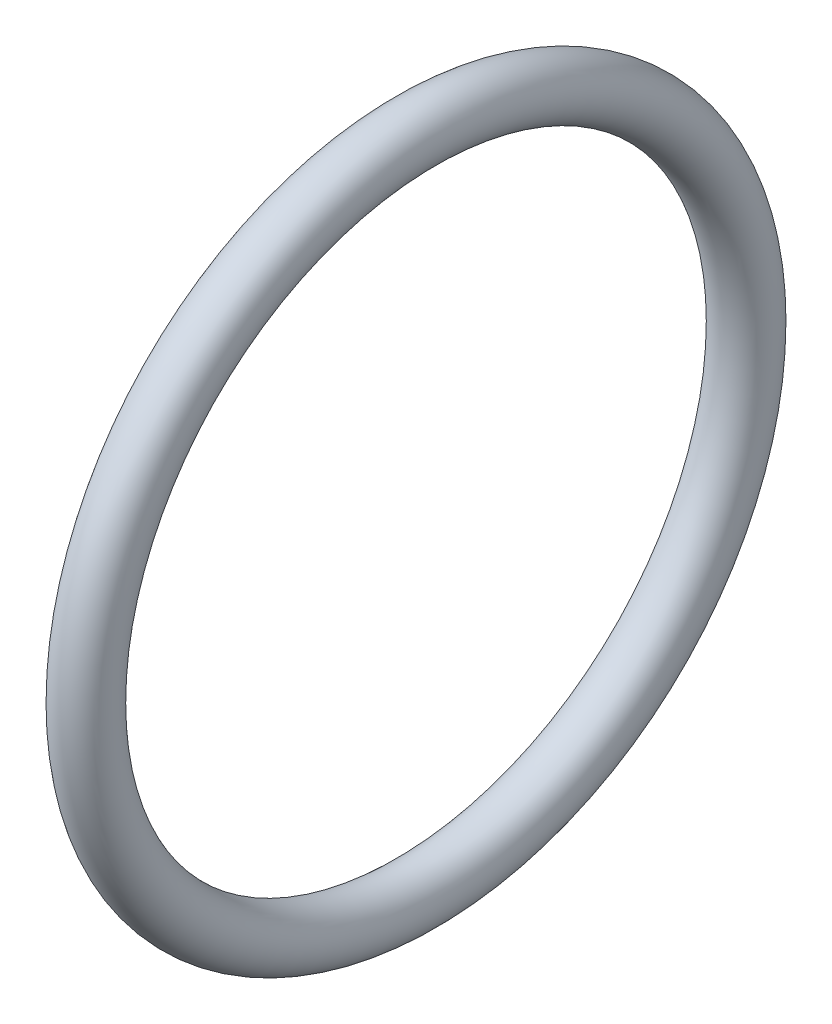
SolidWorks part; units mm, degrees
ref_plane "Front Plane" through (0, 0, 0) normal (0, 0, 1) x (1, 0, 0)
ref_plane "Top Plane" through (0, 0, 0) normal (0, 1, 0) x (1, 0, 0)
ref_plane "Right Plane" through (0, 0, 0) normal (1, 0, 0) x (0, 0, -1)
sketch "Sketch2" plane through (0, 0, 0) normal (0, 0, 1) x (1, 0, 0)
  line L0 (0, 0) -> (58.591, 0) construction
  line L2 (0, 0) -> (18.4, 0)
  line L3 (0, 0) -> (0, 2.5)
  line L4 (0, 2.5) -> (18.4, 2.5)
  line L5 (18.4, 0) -> (18.4, 2.5)
  line L6 (6.0094, 2.5) -> (6.0094, 6)
  line L11 (6.0094, 6) -> (9.9794, 6)
  line L16 (12.9794, 6) -> (12.9794, 3)
  line L17 (12.9794, 3) -> (13.6398, 3)
  line L18 (13.6398, 3) -> (13.6398, 2.5)
  line L19 (13.6398, 2.5) -> (6.0094, 2.5)
  line L22 (13.6398, 2.5) -> (16.1198, 2.5)
  line L23 (13.6398, 2.5) -> (13.6398, 4)
  line L24 (13.6398, 4) -> (16.1198, 4)
  line L25 (16.1198, 2.5) -> (16.1198, 4)
  line L27 (6.0094, 6) -> (9.9794, 6)
  line L28 (6.0094, 6) -> (6.0094, 9)
  line L29 (6.0094, 9) -> (9.9794, 9)
  line L30 (9.9794, 6) -> (9.9794, 9)
  line L31 (6.0094, 9) -> (6.0094, 8.25)
  line L32 (6.0094, 8.25) -> (5.0094, 8.25)
  line L33 (8.6609, 22.001) -> (8.6609, 12.476) construction
  line L34 (5.0094, 12.476) -> (12.3124, 12.476)
  line L35 (9.9794, 9) -> (12.3124, 9)
  line L36 (5.0094, 7.9375) -> (1.8344, 7.9375)
  line L37 (5.0094, 8.25) -> (5.0094, 12.476)
  line L38 (5.0094, 7.9375) -> (5.0094, 13.9365)
  line L39 (5.0094, 13.9365) -> (1.8344, 13.9365)
  line L40 (1.8344, 7.9375) -> (1.8344, 13.9365)
  line L41 (5.0094, 22.001) -> (12.3124, 22.001)
  line L42 (5.0094, 22.001) -> (5.0094, 30.1625)
  line L43 (5.0094, 30.1625) -> (12.3124, 30.1625)
  line L44 (12.3124, 22.001) -> (12.3124, 30.1625)
  line L49 (16.6398, 22.001) -> (16.6398, 7.5)
  line L51 (23.0198, 7.5) -> (23.0198, 6.5)
  line L54 (16.1198, 4) -> (13.6398, 4)
  line L56 (18.0398, 7.5) -> (23.0198, 7.5)
  line L57 (13.3124, 22.001) -> (16.6398, 22.001)
  line L58 (16.1198, 3.5) -> (20.0198, 3.5)
  line L59 (29.9098, 14) -> (26.9098, 11)
  line L60 (4.0094, 31.75) -> (18.0398, 31.75)
  line L61 (18.0398, 7.5) -> (23.0198, 7.5)
  line L62 (18.0398, 7.5) -> (18.0398, 12)
  line L63 (18.0398, 12) -> (23.0198, 12)
  line L64 (23.0198, 7.5) -> (23.0198, 12)
  line L65 (18.0398, 31.75) -> (18.0398, 12)
  line L66 (23.0198, 11) -> (26.9098, 11)
  line L67 (34.8098, 23) -> (31.3098, 19.5)
  line L68 (35.8098, 31) -> (38.7998, 33.99)
  line L69 (29.9098, 14) -> (29.9098, 15)
  line L70 (29.9098, 15) -> (22.9398, 15)
  line L71 (22.9398, 15) -> (21.0398, 15)
  line L72 (18.0398, 7.5) -> (16.6398, 7.5)
  line L73 (21.0398, 15) -> (21.0398, 43)
  line L74 (19.5798, 40) -> (9.6198, 40)
  line L75 (9.6198, 40) -> (4.0094, 40)
  line L76 (21.0398, 43) -> (19.5798, 43)
  line L77 (22.9398, 15) -> (29.9098, 15)
  line L78 (22.9398, 15) -> (22.9398, 21)
  line L79 (22.9398, 21) -> (29.9098, 21)
  line L80 (29.9098, 15) -> (29.9098, 21)
  line L81 (9.6198, 40) -> (19.5798, 40)
  line L82 (9.6198, 40) -> (9.6198, 50)
  line L83 (9.6198, 50) -> (19.5798, 50)
  line L84 (19.5798, 40) -> (19.5798, 50)
  line L85 (4.0094, 40) -> (4.0094, 31.75)
  line L86 (12.9794, 3) -> (12.9794, 2.5)
  line L87 (31.3098, 19.5) -> (29.9098, 19.5)
  line L88 (21.4694, 63.5) -> (21.4694, 51.308)
  line L89 (21.4694, 63.5) -> (25.9398, 63.5)
  line L90 (25.9398, 63.5) -> (25.9398, 25)
  line L91 (27.8398, 25) -> (25.9398, 25)
  line L92 (9.6198, 48) -> (8.1598, 48)
  line L93 (8.1598, 48) -> (8.1598, 53.476)
  line L94 (8.1598, 53.476) -> (19.5798, 53.476)
  line L95 (19.5798, 53.476) -> (19.5798, 50)
  line L96 (13.8698, 63.001) -> (13.8698, 53.476) construction
  line L97 (8.1598, 63.001) -> (19.5798, 63.001)
  line L98 (8.1598, 63.001) -> (8.1598, 68.2625)
  line L99 (8.1598, 68.2625) -> (19.5798, 68.2625)
  line L100 (19.5798, 63.001) -> (19.5798, 68.2625)
  line L101 (12.9794, 6) -> (11.9794, 6)
  line L102 (8.1598, 44.825) -> (4.9848, 44.825)
  line L103 (8.1598, 44.825) -> (8.1598, 54.9365)
  line L104 (8.1598, 54.9365) -> (4.9848, 54.9365)
  line L106 (9.9794, 6) -> (10.8794, 6)
  line L107 (27.8398, 25) -> (34.8098, 25)
  line L108 (34.8098, 25) -> (34.8098, 23)
  line L109 (0, 0) -> (-2, 0)
  line L110 (0, 0) -> (0, 11)
  line L111 (27.8398, 25) -> (34.8098, 25)
  line L112 (27.8398, 25) -> (27.8398, 32.5)
  line L113 (27.8398, 32.5) -> (34.8098, 32.5)
  line L114 (34.8098, 25) -> (34.8098, 32.5)
  line L115 (35.8098, 31) -> (34.8098, 31)
  line L116 (27.8398, 32.5) -> (27.8398, 64.5)
  line L117 (20.5373, 74.025) -> (6.2023, 74.025)
  line L118 (6.2023, 74.025) -> (6.2023, 76.2)
  line L119 (38.7998, 47.29) -> (30.8398, 55.25)
  line L120 (0, 11) -> (-2, 11)
  line L121 (38.7998, 43.815) -> (30.8623, 43.815)
  line L123 (-4.8152, 69.85) -> (1.5348, 76.2)
  line L124 (38.7998, 47.29) -> (38.7998, 33.99)
  line L125 (-2, 0) -> (-2, 11)
  line L126 (38.7998, 37.465) -> (30.8623, 37.465)
  line L127 (30.8623, 43.815) -> (30.8623, 37.465)
  line L128 (6.0094, 2.5) -> (6.0094, 0)
  line L129 (-0.0152, 63.5) -> (-0.0152, 30)
  line L132 (4.9848, 63.5) -> (-0.0152, 63.5)
  line L136 (-1.8152, 30) -> (-11.7752, 30)
  line L138 (-13.7752, 25.4) -> (-2, 25.4)
  line L139 (-2, 25.4) -> (-2, 11.5)
  line L140 (27.8398, 64.5) -> (20.5373, 64.5)
  line L141 (-1.8152, 30) -> (-11.7752, 30)
  line L142 (-1.8152, 30) -> (-1.8152, 39)
  line L143 (-1.8152, 39) -> (-11.7752, 39)
  line L144 (-11.7752, 30) -> (-11.7752, 39)
  line L145 (20.5373, 64.5) -> (20.5373, 74.025)
  line L146 (-12.7752, 37) -> (-12.7752, 47.29)
  line L147 (-12.7752, 37) -> (-11.7752, 37)
  line L148 (30.8398, 55.25) -> (30.8398, 76.2)
  line L149 (11.9794, 6) -> (11.9794, 5.45)
  line L154 (-2, 11.5) -> (0.5, 11.5)
  line L155 (4.9848, 60.6197) -> (24.0348, 60.6197)
  line L160 (4.9848, 60.6197) -> (4.9848, 55.8572)
  line L161 (4.9848, 55.8572) -> (24.0348, 55.8572)
  line L166 (24.0348, 60.6197) -> (24.0348, 55.8572)
  line L167 (4.9848, 60.6197) -> (24.0348, 55.8572) construction
  line L172 (4.9848, 55.8572) -> (24.0348, 60.6197) construction
  line L173 (24.0348, 62.2072) -> (25.9398, 62.2072)
  line L174 (11.9794, 5.45) -> (10.8794, 5.45)
  line L175 (10.8794, 6) -> (10.8794, 5.45)
  line L176 (24.0348, 62.2072) -> (24.0348, 54.2697)
  line L177 (24.0348, 54.2697) -> (25.9398, 54.2697)
  line L178 (25.9398, 62.2072) -> (25.9398, 54.2697)
  line L179 (24.0348, 62.2072) -> (25.9398, 54.2697) construction
  line L180 (24.0348, 54.2697) -> (25.9398, 62.2072) construction
  line L181 (3, 19.6197) -> (15.7, 19.6197)
  line L182 (3, 19.6197) -> (3, 14.8572)
  line L183 (3, 14.8572) -> (15.7, 14.8572)
  line L184 (15.7, 19.6197) -> (15.7, 14.8572)
  line L185 (3, 19.6197) -> (15.7, 14.8572) construction
  line L186 (3, 14.8572) -> (15.7, 19.6197) construction
  line L187 (15.7, 21.2072) -> (16.6398, 21.2072)
  line L188 (15.7, 21.2072) -> (15.7, 13.2697)
  line L189 (15.7, 13.2697) -> (16.6398, 13.2697)
  line L190 (16.6398, 21.2072) -> (16.6398, 13.2697)
  line L191 (15.7, 21.2072) -> (16.6398, 13.2697) construction
  line L192 (15.7, 13.2697) -> (16.6398, 21.2072) construction
  line L193 (0.5, 11.5) -> (0.5, 6.9375)
  line L194 (0.5, 6.9375) -> (1.8344, 6.9375)
  line L195 (23.0198, 6.5) -> (20.0198, 3.5)
  line L196 (4.9848, 63.5) -> (4.9848, 54.9365)
  line L197 (3, 43.825) -> (4.9848, 43.825)
  line L198 (1.8344, 6.9375) -> (1.8344, 7.9375)
  line L199 (6.0094, 0) -> (12.9794, 0)
  line L200 (12.9794, 0) -> (12.9794, 2.5)
  line L201 (18.0398, 31.75) -> (18.0398, 35.875)
  line L202 (18.0398, 35.875) -> (21.0398, 35.875)
  line L203 (30.8398, 76.2) -> (6.2023, 76.2)
  line L204 (2.7573, 69.85) -> (7.2023, 69.85) construction
  line L205 (7.2023, 67.4688) -> (26.2523, 67.4688)
  line L206 (7.2023, 74.025) -> (7.2023, 64.5)
  line L207 (7.2023, 64.5) -> (-1.8152, 64.5)
  line L208 (-1.8152, 64.5) -> (-1.8152, 39)
  line L209 (-12.7752, 47.29) -> (-4.8152, 55.25)
  line L210 (-4.8152, 55.25) -> (-4.8152, 69.85)
  line L211 (7.2023, 67.4688) -> (7.2023, 72.2312)
  line L212 (7.2023, 72.2312) -> (26.2523, 72.2313)
  line L213 (26.2523, 67.4688) -> (26.2523, 72.2313)
  line L214 (26.2523, 73.8187) -> (30.8398, 73.8187)
  line L215 (26.2523, 73.8187) -> (26.2523, 65.8813)
  line L216 (26.2523, 65.8813) -> (30.8398, 65.8813)
  line L217 (30.8398, 73.8187) -> (30.8398, 65.8813)
  line L218 (2.7573, 72.2313) -> (24.9823, 72.2313)
  line L219 (2.7573, 72.2313) -> (2.7573, 67.4687)
  line L220 (2.7573, 67.4687) -> (24.9823, 67.4687)
  line L221 (24.9823, 72.2313) -> (24.9823, 67.4687)
  line L222 (24.9823, 69.85) -> (20.5373, 69.85) construction
  line L223 (21.4694, 51.308) -> (22.9398, 51.308)
  line L224 (22.9398, 51.308) -> (22.9398, 21)
  line L225 (13.6398, 4) -> (13.6398, 12.2697)
  line L226 (13.6398, 12.2697) -> (13.3124, 12.2697)
  line L227 (13.3124, 12.2697) -> (13.3124, 22.001)
  line L228 (12.3124, 9) -> (12.3124, 12.476)
  line L229 (-1.8152, 30) -> (-0.0152, 30)
  line L230 (8.1598, 65.6317) -> (2.7573, 65.6317) construction
  line L231 (19.5798, 65.6317) -> (24.9823, 65.6317) construction
  line L232 (1.5348, 76.2) -> (6.2023, 76.2)
  line L233 (-11.7752, 30) -> (-13.7752, 30)
  line L234 (-13.7752, 30) -> (-13.7752, 25.4)
  line L235 (3, 13.9365) -> (3, 43.825)
  line L236 (4.9848, 54.9365) -> (4.9848, 44.825)
  line L237 (4.9848, 43.825) -> (4.9848, 44.825)
  circle A0 centre (26.8898, 25.95) radius 0.95
  circle A1 centre (21.9898, 15.95) radius 0.95
  circle A2 centre (17.3398, 8.2) radius 0.7
  circle A3 centre (10.4294, 6.45) radius 0.45
  circle A4 centre (-0.9152, 30.9) radius 0.9
  point P7 (24.9873, 58.2385)
  point P131 (16.1699, 17.2385)
  point P135 (14.5098, 58.2385)
  point P146 (9.35, 17.2385)
sketch "Sketch3" plane through (0, 0, 0) normal (0, 0, 1) x (1, 0, 0)
  circle A0 centre (17.3398, 8.2) radius 0.7 construction
  circle A1 centre (17.3398, 8.2) radius 0.7
revolve "Revolve1" add sketch "Sketch3" angle 360 about L0
